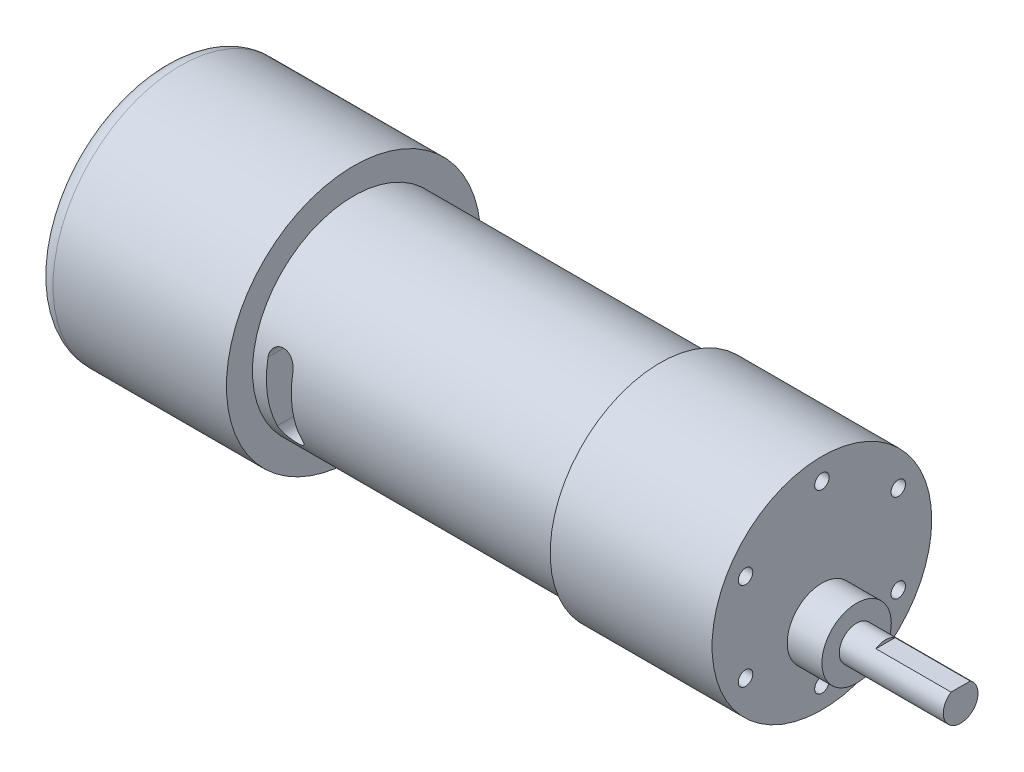
SolidWorks part; units mm, degrees
ref_plane "Front Plane" through (0, 0, 0) normal (0, 0, 1) x (1, 0, 0)
ref_plane "Top Plane" through (0, 0, 0) normal (0, 1, 0) x (1, 0, 0)
ref_plane "Right Plane" through (0, 0, 0) normal (1, 0, 0) x (0, 0, -1)
sketch "Sketch1" plane through (0, 0, 0) normal (1, 0, 0) x (0, 0, -1)
  circle A0 centre (0, 0) radius 22
  dimension "D1" = 44
extrude "Boss-Extrude1" add sketch "Sketch1" along normal blind 33
sketch "Sketch2" plane through (33, 0, 0) normal (1, 0, 0) x (0, 0, -1)
  circle A0 centre (0, 0) radius 17.5
  dimension "D1" = 35
extrude "Boss-Extrude2" add sketch "Sketch2" along normal blind 53
ref_axis "Axis1" through (68.9591, 0, 0) along (-1, 0, 0)
sketch "Sketch4" plane through (86, 0, 0) normal (1, 0, 0) x (0, 0, -1)
  circle A0 centre (0, 0) radius 19
  dimension "D1" = 38
extrude "Boss-Extrude3" add sketch "Sketch4" along normal blind 28
sketch "Sketch12" plane through (0, 0, 0) normal (0, 0, 1) x (1, 0, 0)
  line L0 (37.562, 3.1568) -> (37.562, -7.9305) construction
  line L1 (39.7179, 3.1568) -> (39.7179, -7.9305)
  line L2 (35.4062, 3.1568) -> (35.4062, -7.9305)
  arc A0 (39.7179, 3.1568) -> (35.4062, 3.1568) centre (37.562, 3.1568) ccw
  arc A1 (35.4062, -7.9305) -> (39.7179, -7.9305) centre (37.562, -7.9305) ccw
  point P2 (37.562, -2.3868)
extrude "Cut-Extrude1" cut sketch "Sketch12" along normal through all
ref_plane "Plane1" through (114, 0, 0) normal (1, 0, 0) x (0, 0, -1)
sketch "Sketch13" plane through (114, 0, 0) normal (1, 0, 0) x (0, 0, -1)
  circle A0 centre (0, 15.25) radius 1.25
  circle A1 centre (13.2069, 7.625) radius 1.25
  circle A2 centre (13.2069, -7.625) radius 1.25
  circle A4 centre (0, -15.25) radius 1.25
  circle A5 centre (-13.2069, -7.625) radius 1.25
  circle A6 centre (-13.2069, 7.625) radius 1.25
  point P14 (0, 0)
  dimension "D1" = 2.5
  dimension "D2" = 6
extrude "Cut-Extrude2" cut sketch "Sketch13" against normal blind 3.5
cosmetic thread "Cosmetic Thread10" parameters "D2"=3
sketch "Sketch15" plane through (114, 0, 0) normal (1, 0, 0) x (0, 0, -1)
  line L0 (0, 0) -> (0, -12) construction
  circle A0 centre (0, -6) radius 6
  dimension "D1" = 12
extrude "Boss-Extrude4" add sketch "Sketch15" along normal blind 6
sketch "Sketch16" plane through (114, 0, 0) normal (1, 0, 0) x (0, 0, -1)
  circle A0 centre (0, -6) radius 3
  dimension "D1" = 6
extrude "Boss-Extrude5" add sketch "Sketch16" along normal blind 24
ref_plane "Plane2" through (138, 0, 0) normal (1, 0, 0) x (0, 0, -1)
sketch "Sketch17" plane through (138, 0, 0) normal (1, 0, 0) x (0, 0, -1)
  line L0 (1.6583, -3.5) -> (3, -3.5)
  line L1 (-2.1784, -1.5356) -> (1.6583, -1.5356)
  line L2 (-2.1784, -1.5356) -> (-2.1784, -3.5)
  line L3 (-2.1784, -3.5) -> (1.6583, -3.5)
  line L4 (3, -3.5) -> (3, -1.5356)
  line L5 (3, -1.5356) -> (1.6583, -1.5356)
  circle A0 centre (0, -6) radius 3 construction
  circle A1 centre (0, -6) radius 3 construction
  point P6 (0, -3)
extrude "Cut-Extrude3" cut sketch "Sketch17" against normal blind 13
fillet "Fillet1" radius 3 1 edges at (0, 0, -22)
ref_plane "Plane3" through (0, 0, 0) normal (-1, 0, 0) x (0, 0, 1)
sketch "Sketch18" plane through (0, 0, 0) normal (-1, 0, 0) x (0, 0, 1)
  circle A0 centre (0, 0) radius 1
  dimension "D1" = 2
extrude "Boss-Extrude6" add sketch "Sketch18" along normal blind 5
